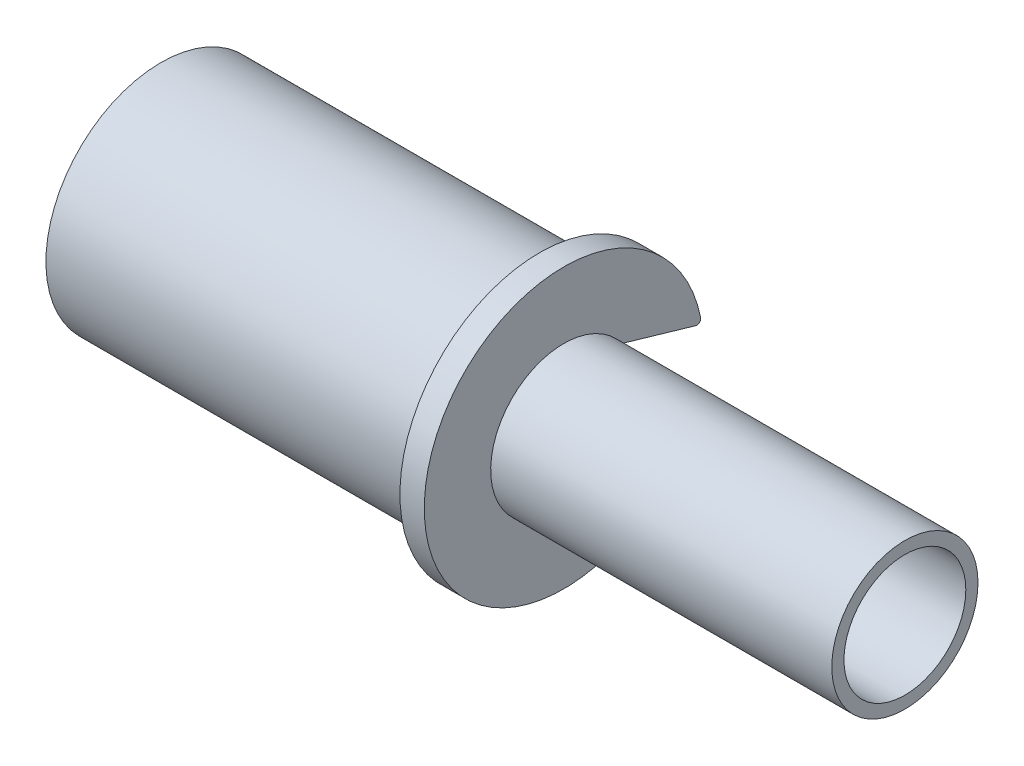
SolidWorks part; units mm, degrees
material "6061-T6 (SS)"
ref_plane "Front Plane" through (0, 0, 0) normal (0, 0, 1) x (1, 0, 0)
ref_plane "Top Plane" through (0, 0, 0) normal (0, 1, 0) x (1, 0, 0)
ref_plane "Right Plane" through (0, 0, 0) normal (1, 0, 0) x (0, 0, -1)
sketch "Sketch1" plane through (0, 0, 0) normal (0, 0, 1) x (1, 0, 0)
  line L0 (0, 0) -> (-16.6687, 0) construction
  line L1 (-3.6156, 3.9687) -> (-3.6156, 4.7625)
  line L2 (-3.6156, 4.7625) -> (-25.8406, 4.7625)
  line L3 (-25.8406, 4.7625) -> (-25.8406, 9.0875)
  line L4 (-25.8406, 9.0875) -> (-27.4281, 9.0875)
  line L5 (-27.4281, 9.0875) -> (-27.4281, 7.5)
  line L6 (-27.4281, 7.5) -> (-52.0781, 7.5)
  line L7 (-52.0781, 7.5) -> (-52.0781, 3.9687)
  line L8 (-52.0781, 3.9687) -> (-3.6156, 3.9687)
  line L11 (-52.0781, -4.2228) -> (-52.0781, 4.2227) construction
  line L12 (-34.4281, 15.2446) -> (-34.4281, -15.2446) construction
  dimension "D1" = 7.9375
  dimension "D4" = 15
  dimension "D3" = 9.525
  dimension "D2" = 1.5875
  dimension "D5" = 1.5875
  dimension "D6" = 7
  dimension "D7" = 22.225
revolve "Revolve1" add sketch "Sketch1" angle 360 about L0
sketch "Sketch4" plane through (-52.0781, 0, 0) normal (-1, 0, 0) x (0, 0, 1)
  line L0 (-2.6604, 9.1459) -> (0, 0) construction
  arc A0 (-10.2214, 9.1698) -> (3.7082, 13.2217) centre (-6.4003, 22.0034) ccw construction
ref_plane "Plane1" through (0, 0, 0) normal (0, 0.2793, 0.9602) x (0, -0.9602, 0.2793)
sketch "Sketch2" plane through (-3.6156, 0, 0) normal (1, 0, 0) x (0, 0, -1)
  line L0 (1.3441, 3.7342) -> (8.2848, 3.7342)
  line L1 (8.2848, -3.7342) -> (1.3441, -3.7342)
  line L2 (0, 0) -> (14.3216, 0) construction
  circle A0 centre (0, 0) radius 3.9687 construction
  circle A1 centre (0, 0) radius 9.0875 construction
  arc A2 (1.3441, 3.7342) -> (1.3441, -3.7342) centre (0, 0) cw
  arc A3 (8.2848, 3.7342) -> (8.2848, -3.7342) centre (0, 0) cw
  arc A4 (3.6742, 3.7342) -> (3.6742, -3.7342) centre (0, 0) cw construction
  circle A5 centre (5.2387, 0) radius 1.27 construction
  circle A6 centre (4.623, 2.4642) radius 1.27 construction
  circle A7 centre (4.623, -2.4642) radius 1.27 construction
  dimension "D1" = 1.27
  dimension "D2" = 2.54
extrude "Cut-Extrude1" [suppressed] cut sketch "Sketch2" against normal through all both
sketch "Sketch3" plane through (0, 0, 0) normal (0, 0.2793, 0.9602) x (1, 0, 0)
  line L1 (-39.3781, 1.4287) -> (-39.3781, -1.4287)
  line L2 (-36.9969, -3.81) -> (-25.8406, -3.81)
  line L3 (-39.3781, 8.89) -> (-39.3781, -8.89) construction
  line L4 (-25.8406, 3.81) -> (-36.9969, 3.81)
  line L5 (-22.6656, -0.635) -> (-22.6656, 0.635)
  line L6 (-22.6656, 0) -> (0, 0) construction
  line L7 (-52.0781, 3.81) -> (-52.0781, -3.81)
  line L8 (-25.8406, -9.0875) -> (-25.8406, 9.0875) construction
  line L9 (-52.0781, 7.5) -> (-52.0781, -7.5) construction
  line L10 (-52.0781, -3.81) -> (-48.9031, -3.81)
  line L11 (-47.3156, -2.2225) -> (-47.3156, 2.2225)
  line L12 (-48.9031, 3.81) -> (-52.0781, 3.81)
  arc A1 (-25.8406, -3.81) -> (-22.6656, -0.635) centre (-25.8406, -0.635) ccw
  arc A2 (-22.6656, 0.635) -> (-25.8406, 3.81) centre (-25.8406, 0.635) ccw
  arc A3 (-39.3781, -1.4287) -> (-36.9969, -3.81) centre (-36.9969, -1.4287) ccw
  arc A4 (-39.3781, 1.4287) -> (-36.9969, 3.81) centre (-36.9969, 1.4287) cw
  arc A5 (-48.9031, -3.81) -> (-47.3156, -2.2225) centre (-48.9031, -2.2225) ccw
  arc A6 (-47.3156, 2.2225) -> (-48.9031, 3.81) centre (-48.9031, 2.2225) ccw
  dimension "D1" = 7.62
  dimension "D2" = 3.175
  dimension "D3" = 2.3813
  dimension "D4" = 1.5875
  dimension "D5" = 3.175
extrude "Cut-Extrude2" cut sketch "Sketch3" against normal up to next
fillet "Fillet1" radius 0.254 12 edges at (-26.6344, 1.3541, -8.9861) (-26.6344, -5.9627, -6.8578) (-32.2125, -5.4627, -5.1389) (-32.2125, 1.854, -7.2672) (-38.8575, -4.7289, -5.8213) (-39.3781, -2.0948, -7.2015) (-38.3557, 1.3802, -7.3719) (-50.4906, 1.854, -7.2672) (-47.6952, 1.2356, -7.3975) (-47.3156, -2.0948, -7.2015) (-48.0025, -5.2376, -5.3682) (-50.4906, -5.4627, -5.1389)
equation "\"bearing1\"=0.273438"
equation "\"D1@Sketch1\"=5/16"
equation "\"D4@Sketch1\"=15mm"
equation "\"D6@Sketch1\"=7mm"
